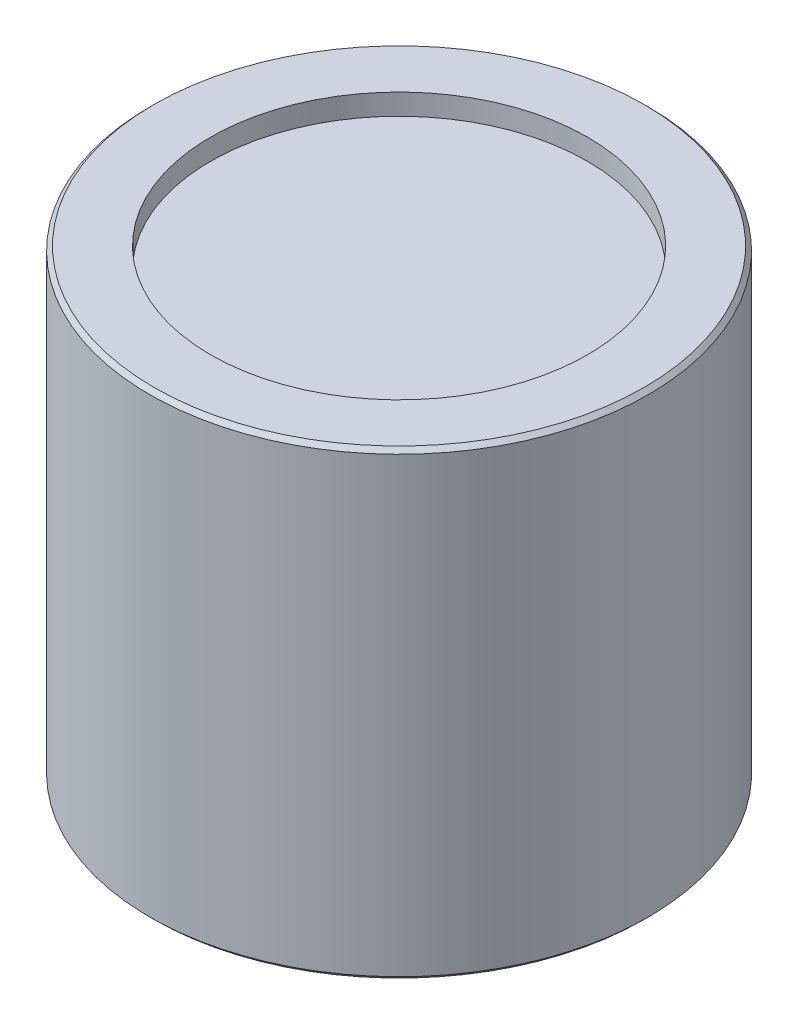
SolidWorks part; units mm, degrees
ref_plane "Ön Düzlem" through (0, 0, 0) normal (0, 0, 1) x (1, 0, 0)
ref_plane "Üst Düzlem" through (0, 0, 0) normal (0, 1, 0) x (1, 0, 0)
ref_plane "Sağ Düzlem" through (0, 0, 0) normal (1, 0, 0) x (0, 0, -1)
sketch "Çizim1" plane through (0, 0, 0) normal (1, 0, 0) x (0, 0, -1)
  line L1 (0, 0) -> (-45, 0)
  line L2 (0, 0) -> (0, 7)
  line L3 (0, 7) -> (-45, 7)
  line L4 (-45, 0) -> (-45, 7)
  line L5 (0, 7) -> (-59.5, 7)
  line L6 (0, 7) -> (0, 117)
  line L7 (0, 117) -> (-59.5, 117)
  line L8 (-59.5, 7) -> (-59.5, 117)
  dimension "D1" = 110
  dimension "D2" = 59.5
  dimension "D3" = 45
  dimension "D4" = 7
revolve "Döndür1" add sketch "Çizim1" angle 360 about L6 region at (0, 3.5, 22.5) region at (0, 62, 29.75)
chamfer "Pah1" distance 1 angle 45 2 edges at (0, 7, -59.5) (0, 117, -59.5)
sketch "Çizim2" plane through (0, 117, 0) normal (0, 1, 0) x (1, 0, 0)
  circle A0 centre (0, 0) radius 45
extrude "Kes-Ekstrüzyon1" cut sketch "Çizim2" against normal blind 5
